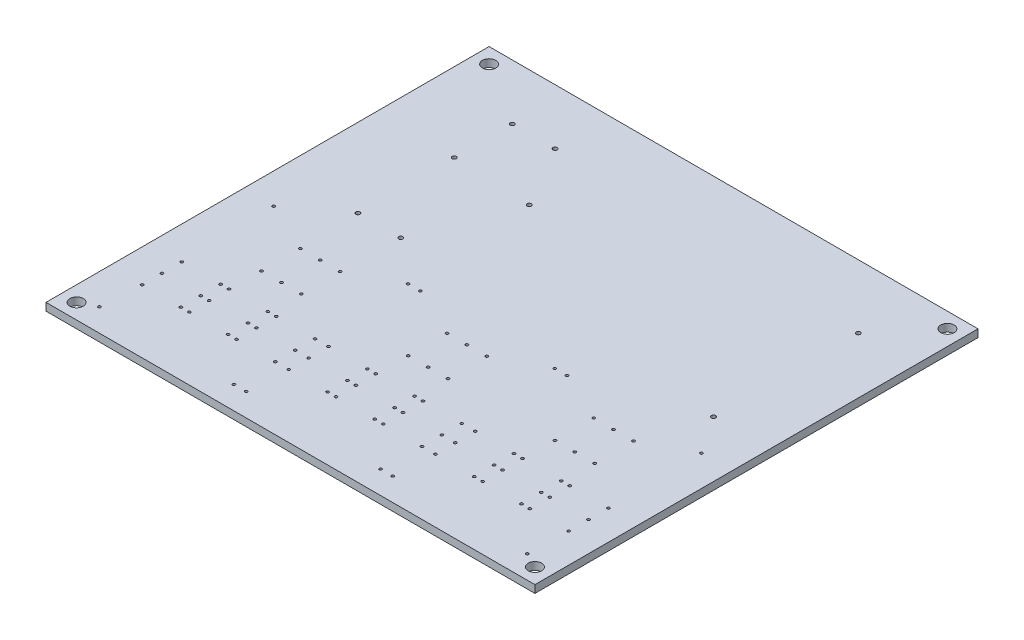
SolidWorks part; units mm, degrees
material "6061-T6 (SS)"
ref_plane "Front Plane" through (0, 0, 0) normal (0, 0, 1) x (1, 0, 0)
ref_plane "Top Plane" through (0, 0, 0) normal (0, 1, 0) x (1, 0, 0)
ref_plane "Right Plane" through (0, 0, 0) normal (1, 0, 0) x (0, 0, -1)
sketch "Sketch1" plane through (0, 0, 0) normal (0, 0, 1) x (1, 0, 0)
  line L1 (0, 0) -> (406.4, 0)
  dimension "D3" = 406.4
sheet metal parameters "Sheet-Metal3" thickness 6.35 parameters "D1"=1.4224
base flange "Base-Flange3" sketch "Sketch1" end condition blind depth 368.3 reverse direction no thickness 6.35 reverse thickness direction yes bend radius 1.4224
sketch "Sketch13" plane through (13.9199, 6.35, 411.98) normal (0, 1, 0) x (0, 0, -1)
  line L0 (62.73, -367.0801) -> (207.51, -367.0801)
  line L1 (207.51, -367.0801) -> (207.51, -255.3201)
  line L2 (207.51, -255.3201) -> (62.73, -255.3201)
  line L3 (112.768, -367.9691) -> (112.768, -255.3201)
  line L4 (207.51, -313.4861) -> (112.768, -313.4861)
  line L5 (62.73, -245.1601) -> (207.51, -245.1601)
  line L6 (207.51, -245.1601) -> (207.51, -133.4001)
  line L7 (207.51, -133.4001) -> (62.73, -133.4001)
  line L8 (112.768, -246.0491) -> (112.768, -133.4001)
  line L9 (207.51, -191.5661) -> (112.768, -191.5661)
  line L10 (62.73, -123.2401) -> (207.51, -123.2401)
  line L11 (207.51, -123.2401) -> (207.51, -11.4801)
  line L12 (207.51, -11.4801) -> (62.73, -11.4801)
  line L13 (112.768, -124.1291) -> (112.768, -11.4801)
  line L14 (207.51, -69.6461) -> (112.768, -69.6461)
  line L15 (62.73, -255.3201) -> (62.73, -367.0801)
  line L16 (62.73, -245.1601) -> (62.73, -133.4001)
  line L17 (62.73, -123.2401) -> (62.73, -11.4801)
  line L18 (112.768, -13.3851) -> (112.768, -45.6431)
  line L19 (43.68, -392.4801) -> (411.98, -392.4801) construction
  line L20 (43.68, 13.9199) -> (43.68, -392.4801) construction
  line L21 (112.768, -13.3851) -> (129.278, -13.3851)
  line L22 (112.768, -45.6431) -> (129.278, -45.6431)
  line L23 (129.278, -13.3851) -> (129.278, -45.6431)
  line L24 (112.768, -13.3851) -> (112.768, -45.6431)
  line L25 (112.768, -13.3851) -> (96.258, -13.3851)
  line L26 (112.768, -45.6431) -> (96.258, -45.6431)
  line L27 (96.258, -13.3851) -> (96.258, -45.6431)
  line L28 (112.768, -52.6281) -> (96.258, -52.6281)
  line L29 (112.768, -52.6281) -> (129.278, -52.6281)
  line L30 (112.768, -84.8861) -> (96.258, -84.8861)
  line L31 (112.768, -84.8861) -> (129.278, -84.8861)
  line L32 (129.278, -52.6281) -> (129.278, -84.8861)
  line L33 (96.258, -52.6281) -> (96.258, -84.8861)
  line L34 (112.768, -91.8711) -> (96.258, -91.8711)
  line L35 (112.768, -91.8711) -> (129.278, -91.8711)
  line L36 (112.768, -124.1291) -> (96.258, -124.1291)
  line L37 (112.768, -124.1291) -> (129.278, -124.1291)
  line L38 (129.278, -91.8711) -> (129.278, -124.1291)
  line L39 (96.258, -91.8711) -> (96.258, -124.1291)
  line L40 (112.768, -135.3051) -> (96.258, -135.3051)
  line L41 (112.768, -135.3051) -> (129.278, -135.3051)
  line L42 (112.768, -167.5631) -> (96.258, -167.5631)
  line L43 (112.768, -167.5631) -> (129.278, -167.5631)
  line L44 (129.278, -135.3051) -> (129.278, -167.5631)
  line L45 (96.258, -135.3051) -> (96.258, -167.5631)
  line L46 (112.768, -206.8061) -> (96.258, -206.8061)
  line L47 (129.278, -174.5481) -> (129.278, -206.8061)
  line L48 (112.768, -174.5481) -> (96.258, -174.5481)
  line L49 (112.768, -206.8061) -> (129.278, -206.8061)
  line L50 (112.768, -174.5481) -> (129.278, -174.5481)
  line L51 (96.258, -174.5481) -> (96.258, -206.8061)
  line L52 (112.768, -246.0491) -> (96.258, -246.0491)
  line L53 (129.278, -213.7911) -> (129.278, -246.0491)
  line L54 (112.768, -213.7911) -> (96.258, -213.7911)
  line L55 (112.768, -246.0491) -> (129.278, -246.0491)
  line L56 (112.768, -213.7911) -> (129.278, -213.7911)
  line L57 (96.258, -213.7911) -> (96.258, -246.0491)
  line L58 (112.768, -289.4831) -> (96.258, -289.4831)
  line L59 (129.278, -257.2251) -> (129.278, -289.4831)
  line L60 (112.768, -257.2251) -> (96.258, -257.2251)
  line L61 (112.768, -289.4831) -> (129.278, -289.4831)
  line L62 (112.768, -257.2251) -> (129.278, -257.2251)
  line L63 (96.258, -257.2251) -> (96.258, -289.4831)
  line L64 (112.768, -328.7261) -> (96.258, -328.7261)
  line L65 (129.278, -296.4681) -> (129.278, -328.7261)
  line L66 (112.768, -296.4681) -> (96.258, -296.4681)
  line L67 (112.768, -328.7261) -> (129.278, -328.7261)
  line L68 (112.768, -296.4681) -> (129.278, -296.4681)
  line L69 (96.258, -296.4681) -> (96.258, -328.7261)
  line L70 (112.768, -367.9691) -> (96.258, -367.9691)
  line L71 (129.278, -335.7111) -> (129.278, -367.9691)
  line L72 (112.768, -335.7111) -> (96.258, -335.7111)
  line L73 (112.768, -367.9691) -> (129.278, -367.9691)
  line L74 (112.768, -335.7111) -> (129.278, -335.7111)
  line L75 (96.258, -335.7111) -> (96.258, -367.9691)
  line L77 (188.079, -86.1561) -> (172.7918, -86.1561)
  line L78 (188.079, -69.6461) -> (188.079, -86.1561)
  line L80 (188.079, -53.1361) -> (155.821, -53.1361)
  line L81 (188.079, -69.6461) -> (188.079, -53.1361)
  line L82 (155.821, -53.1361) -> (155.821, -69.6461)
  line L83 (155.821, -69.6461) -> (155.821, -86.1561)
  line L84 (155.821, -86.1561) -> (188.079, -86.1561)
  line L85 (155.821, -191.5661) -> (155.821, -208.0761)
  line L86 (155.821, -208.0761) -> (188.079, -208.0761)
  line L87 (188.079, -191.5661) -> (188.079, -175.0561)
  line L88 (188.079, -191.5661) -> (188.079, -208.0761)
  line L89 (188.079, -208.0761) -> (172.7918, -208.0761)
  line L90 (188.079, -175.0561) -> (155.821, -175.0561)
  line L91 (155.821, -175.0561) -> (155.821, -191.5661)
  line L92 (155.821, -313.4861) -> (155.821, -329.9961)
  line L93 (155.821, -329.9961) -> (188.079, -329.9961)
  line L94 (188.079, -313.4861) -> (188.079, -296.9761)
  line L95 (188.079, -313.4861) -> (188.079, -329.9961)
  line L96 (188.079, -329.9961) -> (172.7918, -329.9961)
  line L97 (188.079, -296.9761) -> (155.821, -296.9761)
  line L98 (155.821, -296.9761) -> (155.821, -313.4861)
  circle A14 centre (112.768, -296.4681) radius 1.651
  circle A15 centre (112.768, -328.7261) radius 1.651
  circle A16 centre (112.768, -257.2251) radius 1.651
  circle A17 centre (112.768, -289.4831) radius 1.651
  circle A18 centre (112.768, -335.7111) radius 1.651
  circle A19 centre (112.768, -367.9691) radius 1.651
  circle A20 centre (155.821, -313.4861) radius 1.651
  circle A21 centre (188.079, -313.4861) radius 1.651
  circle A22 centre (62.73, -367.0801) radius 2.286
  circle A23 centre (207.51, -367.0801) radius 2.286
  circle A24 centre (62.73, -255.3201) radius 2.286
  circle A25 centre (207.51, -255.3201) radius 2.286
  circle A26 centre (112.768, -174.5481) radius 1.651
  circle A27 centre (112.768, -206.8061) radius 1.651
  circle A28 centre (112.768, -135.3051) radius 1.651
  circle A29 centre (112.768, -167.5631) radius 1.651
  circle A30 centre (112.768, -213.7911) radius 1.651
  circle A31 centre (112.768, -246.0491) radius 1.651
  circle A32 centre (155.821, -191.5661) radius 1.651
  circle A33 centre (188.079, -191.5661) radius 1.651
  circle A34 centre (62.73, -245.1601) radius 2.286
  circle A35 centre (207.51, -245.1601) radius 2.286
  circle A36 centre (62.73, -133.4001) radius 2.286
  circle A37 centre (207.51, -133.4001) radius 2.286
  circle A38 centre (112.768, -52.6281) radius 1.651
  circle A39 centre (112.768, -84.8861) radius 1.651
  circle A40 centre (112.768, -13.3851) radius 1.651
  circle A41 centre (112.768, -45.6431) radius 1.651
  circle A42 centre (112.768, -91.8711) radius 1.651
  circle A43 centre (112.768, -124.1291) radius 1.651
  circle A44 centre (155.821, -69.6461) radius 1.651
  circle A45 centre (188.079, -69.6461) radius 1.651
  circle A46 centre (62.73, -123.2401) radius 2.286
  circle A47 centre (207.51, -123.2401) radius 2.286
  circle A48 centre (62.73, -11.4801) radius 2.286
  circle A49 centre (207.51, -11.4801) radius 2.286
  circle A50 centre (129.278, -13.3851) radius 1.651
  circle A51 centre (129.278, -45.6431) radius 1.651
  circle A52 centre (96.258, -13.3851) radius 1.651
  circle A53 centre (96.258, -45.6431) radius 1.651
  circle A54 centre (96.258, -52.6281) radius 1.651
  circle A55 centre (96.258, -84.8861) radius 1.651
  circle A56 centre (129.278, -52.6281) radius 1.651
  circle A57 centre (129.278, -84.8861) radius 1.651
  circle A58 centre (129.278, -91.8711) radius 1.651
  circle A59 centre (129.278, -124.1291) radius 1.651
  circle A60 centre (96.258, -91.8711) radius 1.651
  circle A61 centre (96.258, -124.1291) radius 1.651
  circle A62 centre (96.258, -135.3051) radius 1.651
  circle A63 centre (96.258, -167.5631) radius 1.651
  circle A64 centre (122.9201, -135.3051) radius 1.651
  circle A65 centre (129.278, -167.5631) radius 1.651
  circle A66 centre (96.258, -206.8061) radius 1.651
  circle A67 centre (129.278, -174.5481) radius 1.651
  circle A68 centre (129.278, -206.8061) radius 1.651
  circle A69 centre (96.258, -174.5481) radius 1.651
  circle A70 centre (96.258, -246.0491) radius 1.651
  circle A71 centre (129.278, -213.7911) radius 1.651
  circle A72 centre (129.278, -246.0491) radius 1.651
  circle A73 centre (96.258, -213.7911) radius 1.651
  circle A74 centre (96.258, -289.4831) radius 1.651
  circle A75 centre (122.9201, -257.2251) radius 1.651
  circle A76 centre (129.278, -289.4831) radius 1.651
  circle A77 centre (96.258, -257.2251) radius 1.651
  circle A78 centre (96.258, -328.7261) radius 1.651
  circle A79 centre (129.278, -296.4681) radius 1.651
  circle A80 centre (129.278, -328.7261) radius 1.651
  circle A81 centre (96.258, -296.4681) radius 1.651
  circle A82 centre (96.258, -367.9691) radius 1.651
  circle A83 centre (129.278, -335.7111) radius 1.651
  circle A84 centre (129.278, -367.9691) radius 1.651
  circle A85 centre (96.2501, -335.7111) radius 1.651
  circle A86 centre (188.079, -86.1561) radius 1.651
  circle A87 centre (155.821, -86.1561) radius 1.651
  circle A88 centre (155.821, -53.1361) radius 1.651
  circle A89 centre (188.079, -53.1361) radius 1.651
  circle A90 centre (188.079, -208.0761) radius 1.651
  circle A91 centre (188.079, -175.0561) radius 1.651
  circle A92 centre (155.821, -208.0761) radius 1.651
  circle A93 centre (155.821, -175.0561) radius 1.651
  circle A94 centre (188.079, -329.9961) radius 1.651
  circle A95 centre (188.079, -296.9761) radius 1.651
  circle A96 centre (155.821, -329.9961) radius 1.651
  circle A97 centre (155.821, -296.9761) radius 1.651
  dimension "D40" = 25.4
  dimension "D2" = 111.76
  dimension "D3" = 144.78
  dimension "D4" = 32.258
  dimension "D5" = 6.985
  dimension "D6" = 43.053
  dimension "D7" = 32.258
  dimension "D8" = 6.985
  dimension "D9" = 32.258
  dimension "D10" = 111.76
  dimension "D11" = 32.258
  dimension "D12" = 50.038
  dimension "D13" = 94.7462
  dimension "D14" = 53.594
  dimension "D15" = 144.78
  dimension "D16" = 111.76
  dimension "D17" = 32.258
  dimension "D18" = 6.985
  dimension "D19" = 43.053
  dimension "D20" = 32.258
  dimension "D21" = 6.985
  dimension "D22" = 32.258
  dimension "D23" = 111.76
  dimension "D24" = 32.258
  dimension "D25" = 53.594
  dimension "D26" = 10.16
  dimension "D27" = 144.78
  dimension "D28" = 111.76
  dimension "D29" = 32.258
  dimension "D30" = 6.985
  dimension "D31" = 43.053
  dimension "D32" = 32.258
  dimension "D33" = 6.985
  dimension "D34" = 32.258
  dimension "D35" = 111.76
  dimension "D36" = 32.258
  dimension "D37" = 53.594
  dimension "D38" = 10.16
  dimension "D39" = 144.78
  dimension "D41" = 19.05
  dimension "D42" = 0.889
  dimension "D43" = 0.889
  dimension "D44" = 0.889
  dimension "D45" = 16.51
  dimension "D46" = 16.51
  dimension "D47" = 16.51
  dimension "D48" = 16.51
  dimension "D49" = 16.51
  dimension "D50" = 16.51
  dimension "D51" = 16.51
  dimension "D52" = 32.258
  dimension "D53" = 16.51
  dimension "D54" = 16.51
  dimension "D55" = 16.51
  dimension "D56" = 16.51
  dimension "D57" = 16.51
sketch "Sketch14" plane through (0, 6.35, 0) normal (0, 1, 0) x (1, 0, 0)
  line L0 (125.0997, -26.162) -> (360.045, -26.162)
  line L1 (360.045, -26.162) -> (360.045, -174.498)
  line L2 (360.045, -174.498) -> (125.0997, -174.498)
  line L3 (125.0997, -174.498) -> (125.0997, -26.162)
  line L4 (119.2577, -26.162) -> (119.2577, -178.562)
  line L5 (119.2577, -178.562) -> (53.2177, -178.562)
  line L6 (53.2177, -178.562) -> (53.2177, -26.162)
  line L7 (53.2177, -26.162) -> (119.2577, -26.162)
  line L8 (130.6877, -26.162) -> (130.6877, -97.282)
  line L9 (130.6877, -97.282) -> (125.0997, -97.282)
  line L10 (271.145, -299.212) -> (271.145, -315.722) construction
  line L11 (125.0997, -52.832) -> (359.7366, -52.832)
  line L12 (359.7366, -52.832) -> (359.7366, -26.162)
  line L13 (359.7366, -174.498) -> (359.7366, -173.228)
  line L14 (65.4097, -26.162) -> (65.4097, -46.1264)
  line L15 (65.4097, -46.1264) -> (65.4097, -94.3864)
  line L16 (65.4097, -94.3864) -> (65.4097, -174.3964)
  line L17 (65.4097, -46.1264) -> (53.2177, -46.1264)
  line L18 (65.4097, -46.1264) -> (100.9697, -46.1264)
  line L19 (65.4097, -174.3964) -> (100.9697, -174.3964)
  line L20 (138.049, -299.212) -> (25.4, -299.212) construction
  circle A0 centre (130.6877, -97.282) radius 2.286
  circle A3 centre (359.7366, -52.832) radius 2.286
  circle A4 centre (359.7366, -173.228) radius 2.286
  circle A5 centre (100.9697, -174.3964) radius 2.286
  circle A6 centre (65.4097, -174.3964) radius 2.286
  circle A7 centre (65.4097, -94.3864) radius 2.286
  circle A8 centre (65.4097, -46.1264) radius 2.286
  circle A9 centre (100.9697, -46.1264) radius 2.286
  dimension "D8" = 4.572
  dimension "D12" = 1.27
  dimension "D13" = 80.01
  dimension "D17" = 120.65
  dimension "D1" = 5.842
  dimension "D2" = 66.04
  dimension "D3" = 234.9453
  dimension "D4" = 152.4
  dimension "D5" = 148.336
  dimension "D6" = 71.12
  dimension "D7" = 5.588
  dimension "D9" = 88.9
  dimension "D11" = 26.67
  dimension "D14" = 48.26
  dimension "D15" = 19.9644
  dimension "D16" = 12.192
sketch "Sketch15" plane through (0, 6.35, 0) normal (0, 1, 0) x (1, 0, 0)
  line L0 (0, -368.3) -> (406.4, -368.3) construction
  line L1 (12.7, -355.6) -> (393.7, -355.6)
  line L2 (12.7, -355.6) -> (12.7, -12.7)
  line L3 (12.7, -12.7) -> (393.7, -12.7)
  line L4 (393.7, -355.6) -> (393.7, -12.7)
  line L5 (406.4, -368.3) -> (406.4, 0) construction
  line L6 (0, -368.3) -> (0, 0) construction
  line L7 (0, 0) -> (406.4, 0) construction
  dimension "D1" = 12.7
  dimension "D2" = 12.7
  dimension "D3" = 12.7
  dimension "D4" = 12.7
hole_wizard "7/16 (0.4375) Diameter Hole1" positions "Sketch16" profile "Sketch17" hole size "7/16" standard "ANSI Inch" end condition through all
sketch "Sketch16" plane through (0, 6.35, 0) normal (0, 1, 0) x (1, 0, 0)
  point P3 (12.7, -355.6)
  point P6 (393.7, -355.6)
  point P9 (393.7, -12.7)
  point P12 (12.7, -12.7)
sketch "Sketch17" plane through (12.7, 6.35, 355.6) normal (1, 0, 0) x (0, 0, 1)
  line L0 (0, 0) -> (0, 6.35)
  line L1 (0, 6.35) -> (5.5562, 6.35)
  line L2 (5.5562, 6.35) -> (5.5562, 0)
  line L5 (5.5562, 0) -> (0, 0)
  line L11 (0, -6.35) -> (0, 107.95) construction
  dimension "Thru Hole Dia." = 11.1125
  dimension "Thru Hole Depth" = 6.35
hole_wizard "#4-40 Tapped Hole2" positions "Sketch25" profile "Sketch26" tap size "#4-40" standard "ANSI Inch" end condition through all
sketch "Sketch25" plane through (0, 6.35, 0) normal (0, 1, 0) x (1, 0, 0)
  point P0 (27.305, -282.702)
  point P17 (59.563, -282.702)
  point P22 (66.548, -282.702)
  point P25 (98.806, -282.702)
  point P28 (105.791, -282.702)
  point P31 (138.049, -282.702)
  point P34 (149.225, -282.702)
  point P37 (181.483, -282.702)
  point P40 (188.468, -282.702)
  point P43 (220.726, -282.702)
  point P46 (227.711, -282.702)
  point P49 (259.969, -282.702)
  point P52 (271.145, -282.702)
  point P55 (303.403, -282.702)
  point P58 (310.388, -282.702)
  point P61 (342.646, -282.702)
  point P64 (349.631, -282.702)
  point P67 (381.889, -282.702)
sketch "Sketch26" plane through (27.305, 6.35, 282.702) normal (1, 0, 0) x (0, 0, 1)
  line L0 (0, 0) -> (0, 6.35)
  line L1 (0, 6.35) -> (1.1303, 6.35)
  line L2 (1.1303, 6.35) -> (1.1303, 0)
  line L5 (1.1303, 0) -> (0, 0)
  line L11 (0, -6.35) -> (0, 107.95) construction
  dimension "Thru Tap Drill Dia." = 2.2606
  dimension "Thru Tap Drill Depth" = 6.35
cosmetic thread "Hole Thread18" parameters "D2"=2.8448
cosmetic thread "Hole Thread23" parameters "D2"=2.8448
cosmetic thread "Hole Thread24" parameters "D2"=2.8448
cosmetic thread "Hole Thread25" parameters "D2"=2.8448
cosmetic thread "Hole Thread26" parameters "D2"=2.8448
cosmetic thread "Hole Thread27" parameters "D2"=2.8448
cosmetic thread "Hole Thread28" parameters "D2"=2.8448
cosmetic thread "Hole Thread29" parameters "D2"=2.8448
cosmetic thread "Hole Thread30" parameters "D2"=2.8448
cosmetic thread "Hole Thread31" parameters "D2"=2.8448
cosmetic thread "Hole Thread32" parameters "D2"=2.8448
cosmetic thread "Hole Thread33" parameters "D2"=2.8448
cosmetic thread "Hole Thread34" parameters "D2"=2.8448
cosmetic thread "Hole Thread35" parameters "D2"=2.8448
cosmetic thread "Hole Thread36" parameters "D2"=2.8448
cosmetic thread "Hole Thread37" parameters "D2"=2.8448
cosmetic thread "Hole Thread38" parameters "D2"=2.8448
cosmetic thread "Hole Thread39" parameters "D2"=2.8448
pattern_linear "LPattern1" count 3 spacing 16.51 along (0, 0, 1) of "#4-40 Tapped Hole2"
cosmetic thread "Hole Thread40" parameters "D2"=2.8448
cosmetic thread "Hole Thread41" parameters "D2"=2.8448
cosmetic thread "Hole Thread42" parameters "D2"=2.8448
cosmetic thread "Hole Thread43" parameters "D2"=2.8448
cosmetic thread "Hole Thread44" parameters "D2"=2.8448
cosmetic thread "Hole Thread45" parameters "D2"=2.8448
cosmetic thread "Hole Thread46" parameters "D2"=2.8448
cosmetic thread "Hole Thread47" parameters "D2"=2.8448
cosmetic thread "Hole Thread48" parameters "D2"=2.8448
cosmetic thread "Hole Thread49" parameters "D2"=2.8448
cosmetic thread "Hole Thread50" parameters "D2"=2.8448
cosmetic thread "Hole Thread51" parameters "D2"=2.8448
cosmetic thread "Hole Thread52" parameters "D2"=2.8448
cosmetic thread "Hole Thread53" parameters "D2"=2.8448
cosmetic thread "Hole Thread54" parameters "D2"=2.8448
cosmetic thread "Hole Thread55" parameters "D2"=2.8448
cosmetic thread "Hole Thread56" parameters "D2"=2.8448
cosmetic thread "Hole Thread57" parameters "D2"=2.8448
cosmetic thread "Hole Thread58" parameters "D2"=2.8448
cosmetic thread "Hole Thread59" parameters "D2"=2.8448
cosmetic thread "Hole Thread60" parameters "D2"=2.8448
cosmetic thread "Hole Thread61" parameters "D2"=2.8448
cosmetic thread "Hole Thread62" parameters "D2"=2.8448
cosmetic thread "Hole Thread63" parameters "D2"=2.8448
cosmetic thread "Hole Thread64" parameters "D2"=2.8448
cosmetic thread "Hole Thread65" parameters "D2"=2.8448
cosmetic thread "Hole Thread66" parameters "D2"=2.8448
cosmetic thread "Hole Thread67" parameters "D2"=2.8448
cosmetic thread "Hole Thread68" parameters "D2"=2.8448
cosmetic thread "Hole Thread69" parameters "D2"=2.8448
cosmetic thread "Hole Thread70" parameters "D2"=2.8448
cosmetic thread "Hole Thread71" parameters "D2"=2.8448
cosmetic thread "Hole Thread72" parameters "D2"=2.8448
cosmetic thread "Hole Thread73" parameters "D2"=2.8448
cosmetic thread "Hole Thread74" parameters "D2"=2.8448
cosmetic thread "Hole Thread75" parameters "D2"=2.8448
hole_wizard "#4-40 Tapped Hole3" positions "Sketch27" profile "Sketch28" tap size "#4-40" standard "ANSI Inch" end condition through all
sketch "Sketch27" plane through (0, 6.35, 0) normal (0, 1, 0) x (1, 0, 0)
  point P0 (67.056, -223.901)
  point P3 (188.976, -223.901)
  point P6 (310.896, -223.901)
sketch "Sketch28" plane through (67.056, 6.35, 223.901) normal (1, 0, 0) x (0, 0, 1)
  line L0 (0, 0) -> (0, 6.35)
  line L1 (0, 6.35) -> (1.1303, 6.35)
  line L2 (1.1303, 6.35) -> (1.1303, 0)
  line L5 (1.1303, 0) -> (0, 0)
  line L11 (0, -6.35) -> (0, 107.95) construction
  dimension "Thru Tap Drill Dia." = 2.2606
  dimension "Thru Tap Drill Depth" = 6.35
cosmetic thread "Hole Thread76" parameters "D2"=2.8448
cosmetic thread "Hole Thread77" parameters "D2"=2.8448
cosmetic thread "Hole Thread78" parameters "D2"=2.8448
pattern_linear "LPattern2" count 3 spacing 16.51 along (1, 0, 0) count 2 spacing 32.258 along (0, 0, 1) of "#4-40 Tapped Hole3"
cosmetic thread "Hole Thread79" parameters "D2"=2.8448
cosmetic thread "Hole Thread80" parameters "D2"=2.8448
cosmetic thread "Hole Thread81" parameters "D2"=2.8448
cosmetic thread "Hole Thread82" parameters "D2"=2.8448
cosmetic thread "Hole Thread83" parameters "D2"=2.8448
cosmetic thread "Hole Thread84" parameters "D2"=2.8448
cosmetic thread "Hole Thread85" parameters "D2"=2.8448
cosmetic thread "Hole Thread86" parameters "D2"=2.8448
cosmetic thread "Hole Thread87" parameters "D2"=2.8448
cosmetic thread "Hole Thread88" parameters "D2"=2.8448
cosmetic thread "Hole Thread89" parameters "D2"=2.8448
cosmetic thread "Hole Thread90" parameters "D2"=2.8448
cosmetic thread "Hole Thread91" parameters "D2"=2.8448
cosmetic thread "Hole Thread92" parameters "D2"=2.8448
cosmetic thread "Hole Thread93" parameters "D2"=2.8448
hole_wizard "#4-40 Tapped Hole1" positions "Sketch29" profile "Sketch30" tap size "#4-40" standard "ANSI Inch" end condition through all
sketch "Sketch29" plane through (0, 6.35, 0) normal (0, 1, 0) x (1, 0, 0)
  point P0 (381, -349.25)
  point P3 (259.08, -349.25)
  point P6 (137.16, -349.25)
sketch "Sketch30" plane through (381, 6.35, 349.25) normal (1, 0, 0) x (0, 0, 1)
  line L0 (0, 0) -> (0, 6.35)
  line L1 (0, 6.35) -> (1.1303, 6.35)
  line L2 (1.1303, 6.35) -> (1.1303, 0)
  line L5 (1.1303, 0) -> (0, 0)
  line L11 (0, -6.35) -> (0, 107.95) construction
  dimension "Thru Tap Drill Dia." = 2.2606
  dimension "Thru Tap Drill Depth" = 6.35
cosmetic thread "Hole Thread94" parameters "D2"=2.8448
cosmetic thread "Hole Thread95" parameters "D2"=2.8448
cosmetic thread "Hole Thread96" parameters "D2"=2.8448
pattern_linear "LPattern3" count 2 spacing 111.76 along (-1, 0, 0) count 2 spacing 144.78 along (0, 0, -1) of "#4-40 Tapped Hole1"
cosmetic thread "Hole Thread97" parameters "D2"=2.8448
cosmetic thread "Hole Thread98" parameters "D2"=2.8448
cosmetic thread "Hole Thread99" parameters "D2"=2.8448
cosmetic thread "Hole Thread100" parameters "D2"=2.8448
cosmetic thread "Hole Thread101" parameters "D2"=2.8448
cosmetic thread "Hole Thread102" parameters "D2"=2.8448
cosmetic thread "Hole Thread103" parameters "D2"=2.8448
cosmetic thread "Hole Thread104" parameters "D2"=2.8448
cosmetic thread "Hole Thread105" parameters "D2"=2.8448
hole_wizard "#8-32 Tapped Hole2" positions "Sketch31" profile "Sketch32" tap size "#8-32" standard "ANSI Inch" end condition through all
sketch "Sketch31" plane through (0, 6.35, 0) normal (0, 1, 0) x (1, 0, 0)
  point P0 (359.7366, -173.228)
  point P3 (359.7366, -52.832)
  point P6 (130.6877, -97.282)
sketch "Sketch32" plane through (359.7366, 6.35, 173.228) normal (1, 0, 0) x (0, 0, 1)
  line L0 (0, 0) -> (0, 6.35)
  line L1 (0, 6.35) -> (1.7272, 6.35)
  line L2 (1.7272, 6.35) -> (1.7272, 0)
  line L5 (1.7272, 0) -> (0, 0)
  line L11 (0, -6.35) -> (0, 107.95) construction
  dimension "Thru Tap Drill Dia." = 3.4544
  dimension "Thru Tap Drill Depth" = 6.35
cosmetic thread "Hole Thread106" parameters "D2"=4.1656
cosmetic thread "Hole Thread107" parameters "D2"=4.1656
cosmetic thread "Hole Thread108" parameters "D2"=4.1656
hole_wizard "#8-32 Tapped Hole1" positions "Sketch33" profile "Sketch34" tap size "#8-32" standard "ANSI Inch" end condition through all
sketch "Sketch33" plane through (0, 6.35, 0) normal (0, 1, 0) x (1, 0, 0)
  point P0 (65.4097, -46.1264)
  point P3 (100.9697, -46.1264)
  point P6 (100.9697, -174.3964)
  point P9 (65.4097, -174.3964)
  point P12 (65.4097, -94.3864)
sketch "Sketch34" plane through (65.4097, 6.35, 46.1264) normal (1, 0, 0) x (0, 0, 1)
  line L0 (0, 0) -> (0, 6.35)
  line L1 (0, 6.35) -> (1.7272, 6.35)
  line L2 (1.7272, 6.35) -> (1.7272, 0)
  line L5 (1.7272, 0) -> (0, 0)
  line L11 (0, -6.35) -> (0, 107.95) construction
  dimension "Thru Tap Drill Dia." = 3.4544
  dimension "Thru Tap Drill Depth" = 6.35
cosmetic thread "Hole Thread109" parameters "D2"=4.1656
cosmetic thread "Hole Thread110" parameters "D2"=4.1656
cosmetic thread "Hole Thread111" parameters "D2"=4.1656
cosmetic thread "Hole Thread112" parameters "D2"=4.1656
cosmetic thread "Hole Thread113" parameters "D2"=4.1656
flat pattern "Flat-Pattern3" [suppressed]
sketch "Bend-Lines3" plane through (0, 1.524, 0) normal (0, 1, 0) x (-1, 0, 0)
sketch3d "Bounding-Box1" [suppressed]
  line L0 (-431.8, 0, 0) -> (0, 0, 0) construction
  line L1 (-431.8, -406.4, 0) -> (0, -406.4, 0) construction
  line L2 (-431.8, 0, 0) -> (-431.8, -406.4, 0) construction
  line L3 (0, 0, 0) -> (0, -406.4, 0) construction
